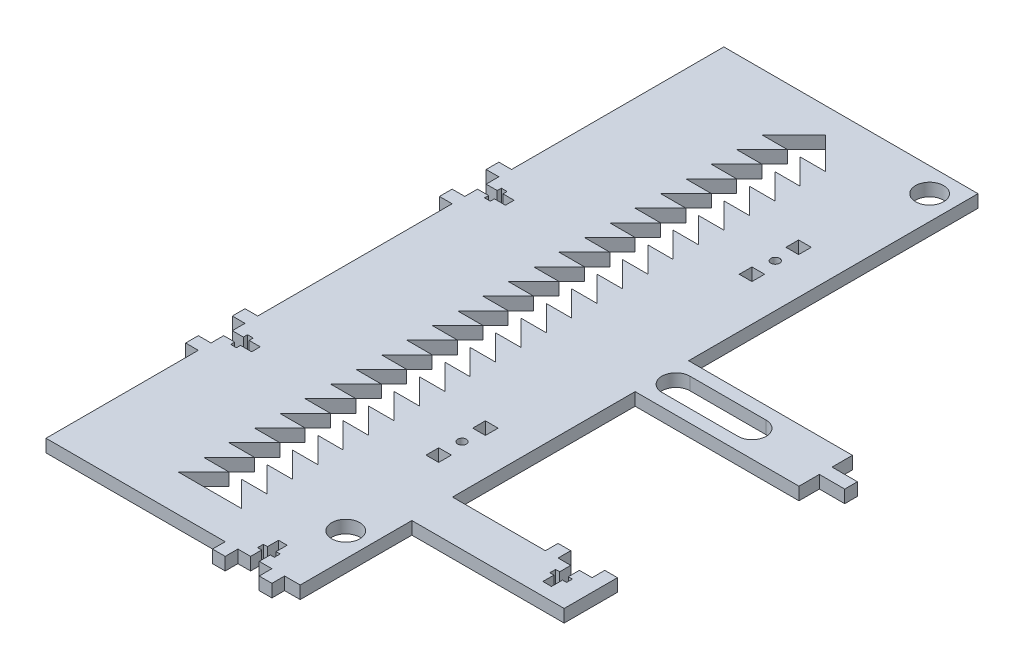
SolidWorks part; units mm, degrees
ref_plane "Front Plane" through (0, 0, 0) normal (0, 0, 1) x (1, 0, 0)
ref_plane "Top Plane" through (0, 0, 0) normal (0, 1, 0) x (1, 0, 0)
ref_plane "Right Plane" through (0, 0, 0) normal (1, 0, 0) x (0, 0, -1)
sketch "Axle Support Plate" plane through (0, 0, 0) normal (0, 1, 0) x (1, 0, 0)
  line L0 (51.4759, 157.4574) -> (51.4759, -134.6426) construction
  line L1 (38.7759, 169.5676) -> (38.7759, -103.4054) construction
  line L2 (0, 156.8676) -> (-15.875, 140.9926)
  line L3 (-15.875, 140.9926) -> (-3.175, 140.9926)
  line L4 (63.5861, -169.5676) -> (63.5861, -113.6876)
  line L5 (-63.5861, 169.5676) -> (63.5861, -169.5676) construction
  line L6 (-63.5861, -169.5676) -> (63.5861, 169.5676) construction
  line L7 (-63.5861, -63.6496) -> (-63.5861, 33.6324)
  line L8 (-63.5861, 169.5676) -> (63.5861, 169.5676)
  line L9 (0, 169.5676) -> (0, -169.5676) construction
  line L10 (15.875, 140.9926) -> (0, 156.8676)
  line L11 (-3.175, 140.9926) -> (-15.875, 128.2926)
  line L12 (-15.875, 128.2926) -> (-3.175, 128.2926)
  line L13 (15.875, 128.2926) -> (3.175, 140.9926)
  line L14 (-3.175, 128.2926) -> (-15.875, 115.5926)
  line L15 (-15.875, 115.5926) -> (-3.175, 115.5926)
  line L16 (15.875, 115.5926) -> (3.175, 128.2926)
  line L17 (63.5861, 11.4074) -> (4.2777, 11.4074) construction
  line L18 (-3.175, 115.5926) -> (-15.875, 102.8926)
  line L19 (-15.875, 102.8926) -> (-3.175, 102.8926)
  line L20 (15.875, 102.8926) -> (3.175, 115.5926)
  line L21 (-3.175, 102.8926) -> (-15.875, 90.1926)
  line L22 (-15.875, 90.1926) -> (-3.175, 90.1926)
  line L23 (55.7939, -169.5676) -> (63.5861, -169.5676)
  line L24 (15.875, 90.1926) -> (3.175, 102.8926)
  line L25 (-3.175, 90.1926) -> (-15.875, 77.4926)
  line L26 (-15.875, 77.4926) -> (-3.175, 77.4926)
  line L27 (15.875, 77.4926) -> (3.175, 90.1926)
  line L28 (-3.175, 77.4926) -> (-15.875, 64.7926)
  line L29 (-15.875, 64.7926) -> (-3.175, 64.7926)
  line L30 (15.875, 64.7926) -> (3.175, 77.4926)
  line L31 (-3.175, 64.7926) -> (-15.875, 52.0926)
  line L32 (-15.875, 52.0926) -> (-3.175, 52.0926)
  line L33 (15.875, 52.0926) -> (3.175, 64.7926)
  line L34 (-3.175, 52.0926) -> (-15.875, 39.3926)
  line L35 (-15.875, 39.3926) -> (-3.175, 39.3926)
  line L36 (15.875, 39.3926) -> (3.175, 52.0926)
  line L37 (63.5861, 24.7876) -> (145.5462, 24.7876)
  line L38 (145.5462, 24.7876) -> (145.5462, 14.5824)
  line L39 (145.5462, -1.9727) -> (63.5861, -1.9727)
  line L40 (70.6162, 11.4074) -> (108.7162, 11.4074) construction
  line L41 (70.6162, 18.4376) -> (108.7162, 18.4376)
  line L42 (70.6162, 4.3773) -> (108.7162, 4.3773)
  line L43 (145.5462, 8.2324) -> (158.2462, 8.2324)
  line L44 (158.2462, 8.2324) -> (158.2462, 14.5824)
  line L45 (158.2462, 14.5824) -> (145.5462, 14.5824)
  line L46 (63.5861, 24.7876) -> (63.5861, 169.5676)
  line L47 (63.5861, 24.7876) -> (63.5861, -1.9727) construction
  line L48 (63.5861, 11.4074) -> (158.2462, 11.4074) construction
  line L49 (-3.175, 39.3926) -> (-15.875, 26.6926)
  line L50 (-15.875, 26.6926) -> (-3.175, 26.6926)
  line L51 (145.5462, 8.2324) -> (145.5462, -1.9727)
  line L52 (15.875, 26.6926) -> (3.175, 39.3926)
  line L53 (-3.175, 26.6926) -> (-15.875, 13.9926)
  line L54 (-15.875, 13.9926) -> (-3.175, 13.9926)
  line L55 (15.875, 13.9926) -> (3.175, 26.6926)
  line L56 (-3.175, 13.9926) -> (-15.875, 1.2926)
  line L57 (-15.875, 1.2926) -> (-3.175, 1.2926)
  line L58 (15.875, 1.2926) -> (3.175, 13.9926)
  line L59 (3.175, -11.4074) -> (15.875, -11.4074)
  line L60 (-15.875, -11.4074) -> (-3.175, -11.4074)
  line L61 (15.875, -11.4074) -> (3.175, 1.2926)
  line L62 (-3.175, -11.4074) -> (-15.875, -24.1074)
  line L63 (-15.875, -24.1074) -> (-3.175, -24.1074)
  line L64 (15.875, -24.1074) -> (3.175, -11.4074)
  line L65 (-3.175, -24.1074) -> (-15.875, -36.8074)
  line L66 (-15.875, -36.8074) -> (-3.175, -36.8074)
  line L67 (15.875, -36.8074) -> (3.175, -24.1074)
  line L68 (-3.175, -36.8074) -> (-15.875, -49.5074)
  line L69 (-15.875, -49.5074) -> (-3.175, -49.5074)
  line L70 (15.875, -49.5074) -> (3.175, -36.8074)
  line L71 (-3.175, -49.5074) -> (-15.875, -62.2074)
  line L72 (-15.875, -62.2074) -> (-3.175, -62.2074)
  line L73 (15.875, -62.2074) -> (3.175, -49.5074)
  line L74 (-3.175, -62.2074) -> (-15.875, -74.9074)
  line L75 (-15.875, -74.9074) -> (-3.175, -74.9074)
  line L76 (15.875, -74.9074) -> (3.175, -62.2074)
  line L77 (-3.175, -74.9074) -> (-15.875, -87.6074)
  line L78 (-15.875, -87.6074) -> (-3.175, -87.6074)
  line L79 (15.875, -87.6074) -> (3.175, -74.9074)
  line L80 (-3.175, -87.6074) -> (-15.875, -100.3074)
  line L81 (-63.5861, 63.3504) -> (-63.5861, 169.5676)
  line L82 (-15.875, -100.3074) -> (-3.175, -100.3074)
  line L83 (15.875, -100.3074) -> (3.175, -87.6074)
  line L84 (-3.175, -100.3074) -> (-15.875, -113.0074)
  line L85 (-15.875, -113.0074) -> (-3.175, -113.0074)
  line L86 (15.875, -113.0074) -> (3.175, -100.3074)
  line L87 (-3.175, -113.0074) -> (-15.875, -125.7074)
  line L88 (-15.875, -125.7074) -> (-3.175, -125.7074)
  line L89 (15.875, -125.7074) -> (3.175, -113.0074)
  line L90 (26.0759, -169.5676) -> (-63.5861, -169.5676)
  line L91 (-3.175, -125.7074) -> (-15.875, -138.4074)
  line L92 (-15.875, -138.4074) -> (-3.175, -138.4074)
  line L93 (15.875, -138.4074) -> (3.175, -125.7074)
  line L94 (-63.5861, -169.5676) -> (-63.5861, -93.3676)
  line L95 (-3.175, -138.4074) -> (-15.875, -151.1074)
  line L96 (-15.875, -151.1074) -> (15.875, -151.1074)
  line L97 (15.875, -151.1074) -> (3.175, -138.4074)
  line L98 (3.175, 140.9926) -> (15.875, 140.9926)
  line L99 (3.175, 115.5926) -> (15.875, 115.5926)
  line L100 (3.175, 128.2926) -> (15.875, 128.2926)
  line L101 (3.175, 102.8926) -> (15.875, 102.8926)
  line L102 (3.175, 77.4926) -> (15.875, 77.4926)
  line L103 (3.175, 90.1926) -> (15.875, 90.1926)
  line L104 (3.175, 64.7926) -> (15.875, 64.7926)
  line L105 (3.175, 52.0926) -> (15.875, 52.0926)
  line L106 (3.175, 39.3926) -> (15.875, 39.3926)
  line L107 (3.175, 26.6926) -> (15.875, 26.6926)
  line L108 (3.175, 13.9926) -> (15.875, 13.9926)
  line L109 (3.175, 1.2926) -> (15.875, 1.2926)
  line L110 (-3.175, 1.2926) -> (-15.875, -11.4074)
  line L111 (0, 4.4676) -> (-1.2184, 3.2492) [skipped]
  line L112 (3.175, -24.1074) -> (15.875, -24.1074)
  line L113 (3.175, -36.8074) -> (15.875, -36.8074)
  line L114 (3.175, -49.5074) -> (15.875, -49.5074)
  line L115 (3.175, -62.2074) -> (15.875, -62.2074)
  line L116 (3.175, -74.9074) -> (15.875, -74.9074)
  line L117 (3.175, -87.6074) -> (15.875, -87.6074)
  line L118 (3.175, -100.3074) -> (15.875, -100.3074)
  line L119 (3.175, -113.0074) -> (15.875, -113.0074)
  line L120 (3.175, -125.7074) -> (15.875, -125.7074)
  line L121 (3.175, -138.4074) -> (15.875, -138.4074)
  line L122 (139.7861, -93.3676) -> (139.7861, -113.6876)
  line L123 (139.7861, -113.6876) -> (63.5861, -113.6876)
  line L124 (110.0681, -93.3676) -> (63.5861, -93.3676)
  line L125 (63.5861, -93.3676) -> (63.5861, -1.9727)
  circle A0 centre (51.4759, 157.4574) radius 7.0301
  circle A1 centre (51.4759, -134.6426) radius 7.0301
  arc A4 (70.6162, 18.4376) -> (70.6162, 4.3773) centre (70.6162, 11.4074) ccw
  arc A5 (108.7162, 4.3773) -> (108.7162, 18.4376) centre (108.7162, 11.4074) ccw
  point P8 (0, 0)
  point P15 (51.4759, 11.4074)
  point P57 (89.6662, 11.4074)
  line B0 (-63.5861, -69.9996) -> (-69.9361, -69.9996)
  line B1 (-69.9361, -69.9996) -> (-69.9361, -63.6496)
  line B2 (-69.9361, -63.6496) -> (-63.5861, -63.6496)
  line B3 (-63.5861, -76.3496) -> (-58.0511, -76.3496)
  line B4 (-58.0511, -76.3496) -> (-58.0511, -74.3086)
  line B5 (-58.0511, -74.3086) -> (-55.1511, -74.3086)
  line B6 (-55.1511, -74.3086) -> (-55.1511, -76.3496)
  line B7 (-55.1511, -76.3496) -> (-49.6161, -76.3496)
  line B8 (-49.6161, -76.3496) -> (-49.6161, -80.6676)
  line B9 (-49.6161, -80.6676) -> (-55.1511, -80.6676)
  line B10 (-55.1511, -80.6676) -> (-55.1511, -82.7086)
  line B11 (-55.1511, -82.7086) -> (-58.0511, -82.7086)
  line B12 (-58.0511, -82.7086) -> (-58.0511, -80.6676)
  line B13 (-58.0511, -80.6676) -> (-63.5861, -80.6676)
  line B14 (-49.6161, -78.5086) -> (-63.5861, -78.5086) construction
  line B15 (-63.5861, -87.0176) -> (-63.5861, -80.6676)
  line B16 (-69.9361, -93.3676) -> (-63.5861, -93.3676)
  line B17 (-63.5861, -69.9996) -> (-63.5861, -76.3496)
  line B18 (-69.9361, -87.0176) -> (-69.9361, -93.3676)
  line B19 (-63.5861, -87.0176) -> (-69.9361, -87.0176)
  line B20 (-63.5861, 57.0004) -> (-69.9361, 57.0004)
  line B21 (-69.9361, 57.0004) -> (-69.9361, 63.3504)
  line B22 (-69.9361, 63.3504) -> (-63.5861, 63.3504)
  line B23 (-63.5861, 50.6504) -> (-58.0511, 50.6504)
  line B24 (-58.0511, 50.6504) -> (-58.0511, 52.6914)
  line B25 (-58.0511, 52.6914) -> (-55.1511, 52.6914)
  line B26 (-55.1511, 52.6914) -> (-55.1511, 50.6504)
  line B27 (-55.1511, 50.6504) -> (-49.6161, 50.6504)
  line B28 (-49.6161, 50.6504) -> (-49.6161, 46.3324)
  line B29 (-49.6161, 46.3324) -> (-55.1511, 46.3324)
  line B30 (-55.1511, 46.3324) -> (-55.1511, 44.2914)
  line B31 (-55.1511, 44.2914) -> (-58.0511, 44.2914)
  line B32 (-58.0511, 44.2914) -> (-58.0511, 46.3324)
  line B33 (-58.0511, 46.3324) -> (-63.5861, 46.3324)
  line B34 (-49.6161, 48.4914) -> (-63.5861, 48.4914) construction
  line B35 (-63.5861, 39.9824) -> (-63.5861, 46.3324)
  line B36 (-69.9361, 33.6324) -> (-63.5861, 33.6324)
  line B37 (-63.5861, 57.0004) -> (-63.5861, 50.6504)
  line B38 (-69.9361, 39.9824) -> (-69.9361, 33.6324)
  line B39 (-63.5861, 39.9824) -> (-69.9361, 39.9824)
  line B40 (32.4259, -169.5676) -> (32.4259, -175.9176)
  line B41 (32.4259, -175.9176) -> (26.0759, -175.9176)
  line B42 (26.0759, -175.9176) -> (26.0759, -169.5676)
  line B43 (38.7759, -169.5676) -> (38.7759, -164.0326)
  line B44 (38.7759, -164.0326) -> (36.7349, -164.0326)
  line B45 (36.7349, -164.0326) -> (36.7349, -161.1326)
  line B46 (36.7349, -161.1326) -> (38.7759, -161.1326)
  line B47 (38.7759, -161.1326) -> (38.7759, -155.5976)
  line B48 (38.7759, -155.5976) -> (43.0939, -155.5976)
  line B49 (43.0939, -155.5976) -> (43.0939, -161.1326)
  line B50 (43.0939, -161.1326) -> (45.1349, -161.1326)
  line B51 (45.1349, -161.1326) -> (45.1349, -164.0326)
  line B52 (45.1349, -164.0326) -> (43.0939, -164.0326)
  line B53 (43.0939, -164.0326) -> (43.0939, -169.5676)
  line B54 (40.9349, -155.5976) -> (40.9349, -169.5676) construction
  line B55 (49.4439, -169.5676) -> (43.0939, -169.5676)
  line B56 (55.7939, -175.9176) -> (55.7939, -169.5676)
  line B57 (32.4259, -169.5676) -> (38.7759, -169.5676)
  line B58 (49.4439, -175.9176) -> (55.7939, -175.9176)
  line B59 (49.4439, -169.5676) -> (49.4439, -175.9176)
  line B60 (41.9509, 74.9074) -> (41.9509, 104.6254) construction
  line B61 (39.7919, 89.7664) -> (44.1099, 89.7664) construction
  line B62 (38.7759, 98.2754) -> (45.1259, 98.2754)
  line B63 (38.7759, 98.2754) -> (38.7759, 104.6254)
  line B64 (38.7759, 104.6254) -> (45.1259, 104.6254)
  line B65 (45.1259, 98.2754) -> (45.1259, 104.6254)
  line B66 (38.7759, 98.2754) -> (45.1259, 104.6254) construction
  line B67 (38.7759, 104.6254) -> (45.1259, 98.2754) construction
  line B68 (38.7759, 74.9074) -> (45.1259, 81.2574) construction
  line B69 (38.7759, 81.2574) -> (45.1259, 74.9074) construction
  line B70 (45.1259, 81.2574) -> (45.1259, 74.9074)
  line B71 (38.7759, 74.9074) -> (45.1259, 74.9074)
  line B72 (38.7759, 81.2574) -> (38.7759, 74.9074)
  line B73 (38.7759, 81.2574) -> (45.1259, 81.2574)
  circle B74 centre (41.9509, 89.7664) radius 2.159
  line B75 (41.9509, -52.0926) -> (41.9509, -81.8106) construction
  line B76 (39.7919, -66.9516) -> (44.1099, -66.9516) construction
  line B77 (38.7759, -75.4606) -> (45.1259, -75.4606)
  line B78 (38.7759, -75.4606) -> (38.7759, -81.8106)
  line B79 (38.7759, -81.8106) -> (45.1259, -81.8106)
  line B80 (45.1259, -75.4606) -> (45.1259, -81.8106)
  line B81 (38.7759, -75.4606) -> (45.1259, -81.8106) construction
  line B82 (38.7759, -81.8106) -> (45.1259, -75.4606) construction
  line B83 (38.7759, -52.0926) -> (45.1259, -58.4426) construction
  line B84 (38.7759, -58.4426) -> (45.1259, -52.0926) construction
  line B85 (45.1259, -58.4426) -> (45.1259, -52.0926)
  line B86 (38.7759, -52.0926) -> (45.1259, -52.0926)
  line B87 (38.7759, -58.4426) -> (38.7759, -52.0926)
  line B88 (38.7759, -58.4426) -> (45.1259, -58.4426)
  circle B89 centre (41.9509, -66.9516) radius 2.159
  line B90 (133.4361, -93.3676) -> (133.4361, -87.0176)
  line B91 (133.4361, -87.0176) -> (139.7861, -87.0176)
  line B92 (139.7861, -87.0176) -> (139.7861, -93.3676)
  line B93 (127.0861, -93.3676) -> (127.0861, -98.9026)
  line B94 (127.0861, -98.9026) -> (129.1271, -98.9026)
  line B95 (129.1271, -98.9026) -> (129.1271, -101.8026)
  line B96 (129.1271, -101.8026) -> (127.0861, -101.8026)
  line B97 (127.0861, -101.8026) -> (127.0861, -107.3376)
  line B98 (127.0861, -107.3376) -> (122.7681, -107.3376)
  line B99 (122.7681, -107.3376) -> (122.7681, -101.8026)
  line B100 (122.7681, -101.8026) -> (120.7271, -101.8026)
  line B101 (120.7271, -101.8026) -> (120.7271, -98.9026)
  line B102 (120.7271, -98.9026) -> (122.7681, -98.9026)
  line B103 (122.7681, -98.9026) -> (122.7681, -93.3676)
  line B104 (124.9271, -107.3376) -> (124.9271, -93.3676) construction
  line B105 (116.4181, -93.3676) -> (122.7681, -93.3676)
  line B106 (110.0681, -87.0176) -> (110.0681, -93.3676)
  line B107 (133.4361, -93.3676) -> (127.0861, -93.3676)
  line B108 (116.4181, -87.0176) -> (110.0681, -87.0176)
  line B109 (116.4181, -93.3676) -> (116.4181, -87.0176)
  dimension "D1" = 5.08
  dimension "D4" = 14.0603
  dimension "D5" = 5.08
  dimension "D8" = 31.75
  dimension "D14" = 14.0603
  dimension "D15" = 76.2
  dimension "D16" = 6.35
  dimension "D22" = 7.0301
  dimension "D25" = 36.83
  dimension "D2" = 292.1
  dimension "D6" = 12.7
  dimension "D7" = 63.5
  dimension "D9" = 89.662
  dimension "D10" = 12.7
  dimension "D11" = 24
  dimension "D12" = 10.541
  dimension "D13" = 34.925
  dimension "D17" = 76.2
  dimension "D23" = 6.35
  dimension "D24" = 38.1
  dimension "D26" = 12.7
  dimension "D27" = 6.35
  dimension "D29" = 76.2
  dimension "D30" = 203.2
sketch_block_instance "Male T-slot assembly-1"
sketch_block "Male T-slot assembly" parameters "D1"=6.35, "D2"=6.35, "D3"=4.318, "D4"=2.9, "D5"=8.4, "D6"=13.97, "D7"=6.35
sketch_block_instance "Male T-slot assembly-2"
sketch_block_instance "Male T-slot assembly-4"
sketch_block_instance "Female T-Slot Assembly-1"
sketch_block "Female T-Slot Assembly" parameters "D4"=4.318, "D1"=6.35, "D2"=6.35, "D3"=6.35
sketch_block_instance "Female T-Slot Assembly-3"
sketch_block_instance "Male T-slot assembly-6"
extrude "Boss-Extrude1" add sketch "Axle Support Plate" along normal blind 6.35 contours L23 L4 L39 L51 L43 L44 L45 L38 L37 L46 L8 region at (59.69, 0, 165.4272)
equation "\"Ball Diameter\"= 1.75in"
equation "\"Sheet Thickness\"= 0.25in"
equation "\"Screw Diameter\"= .17in"
equation "\"Robot Diameter\"= 14in"
equation "\"Castor Screw Diameter\"= 0.22in"
equation "\"Wheel Diameter\" = 4in"
equation "\"Nut Diameter\" = 8.4mm"
equation "\"Nut Height\" = 2.9mm"
equation "\"Screw Height\" = 0.55in"
equation "\"Pulley Diameter\" = 1in"
equation "\"Reactor Height\" = 14in"
equation "\"Elevator Height\" = 11.5in"
equation "\"Elevator Width\" = \"Ball Diameter\" + 0.25in"
equation "\"D1@Boss-Extrude1\"=\"Sheet Thickness\""
equation "\"Elevator Bearing Diameter\" = sqr(2*(\"Sheet Thickness\"^2)) + 0.2in"
equation "\"Elevator Axle Length\" = \"Elevator Width\" + 8*\"Sheet Thickness\""
equation "\"D4@Axle Support Plate\"=\"Elevator Bearing Diameter\""
equation "\"D6@Axle Support Plate\"=(\"Pulley Diameter\")/2"
equation "\"D13@Axle Support Plate\"=2.5in - \"Sheet Thickness\" - (\"Ball Diameter\")/2"
equation "\"D9@Axle Support Plate\"=\"Elevator Clearance from Axis\" + \"Sheet Thickness\""
equation "\"D14@Axle Support Plate\" = \"Elevator Bearing Diameter\""
equation "\"D22@Axle Support Plate\"=\"Elevator Bearing Diameter\"/2"
equation "\"D23@Axle Support Plate\" = \"Sheet Thickness\""
equation "\"Elevator Axle Endcap Diameter\" = \"Pulley Diameter\" + 0.25in"
equation "\"D25@Axle Support Plate\"=\"Elevator Axle Endcap Diameter\"+0.2in"
equation "\"D27@Axle Support Plate\"=\"Sheet Thickness\""
equation "\"Elevator Clearance from Axis\" = 3.28in"
